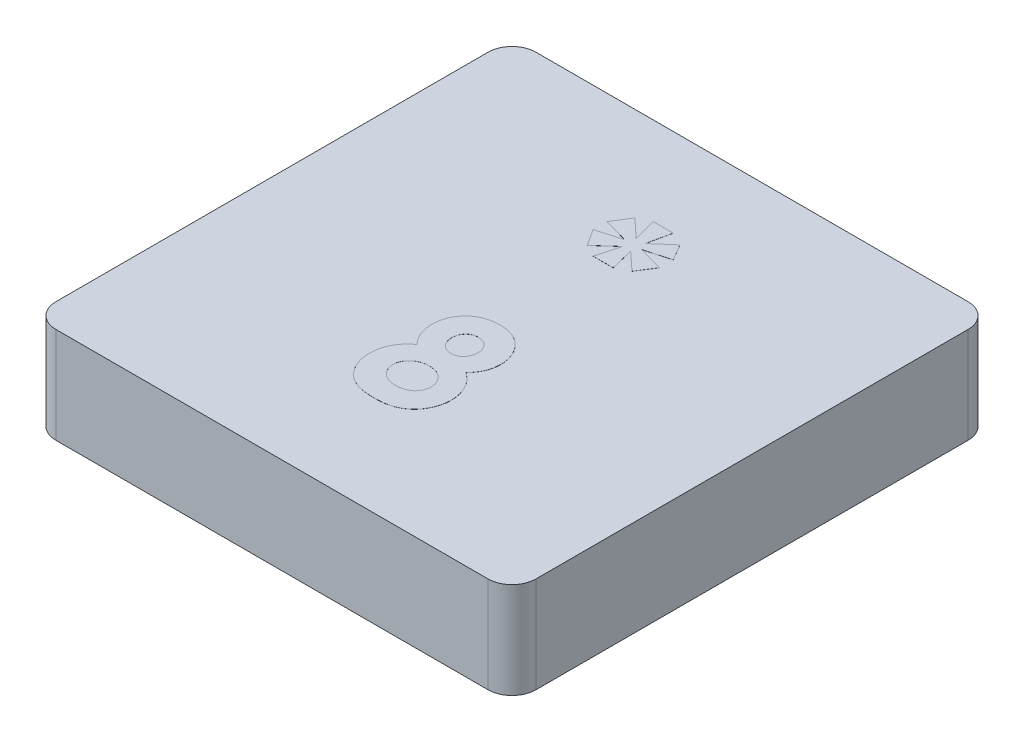
SolidWorks part; units mm, degrees
ref_plane "Front Plane" through (0, 0, 0) normal (0, 0, 1) x (1, 0, 0)
ref_plane "Top Plane" through (0, 0, 0) normal (0, 1, 0) x (1, 0, 0)
ref_plane "Right Plane" through (0, 0, 0) normal (1, 0, 0) x (0, 0, -1)
sketch "Sketch1" plane through (0, 0, 0) normal (0, 1, 0) x (1, 0, 0)
  line L0 (0, 0) -> (12.7, 0)
  line L1 (12.7, 0) -> (12.7, 12.7)
  line L2 (12.7, 12.7) -> (0, 12.7)
  line L3 (0, 12.7) -> (0, 0)
  dimension "D1" = 12.7
  dimension "D2" = 12.7
extrude "Boss-Extrude1" add sketch "Sketch1" along normal blind 2.54
fillet "Fillet1" radius 0.635 4 edges at (0, 1.27, -12.7) (12.7, 1.27, -12.7) (12.7, 1.27, 0) (0, 1.27, 0)
shell "Shell1" thickness 0.635 removed face at (6.35, 0, -6.35)
sketch "Sketch2" plane through (0, 1.905, 0) normal (0, -1, 0) x (-1, 0, 0)
  line L0 (-0.635, 6.35) -> (-12.065, 6.35) construction
  line L1 (-0.635, 12.065) -> (-0.635, 0.635) construction
  line L2 (-12.065, 0.635) -> (-12.065, 12.065) construction
  line L3 (-6.35, 0.635) -> (-6.35, 12.065) construction
  line L4 (-0.635, 0.635) -> (-12.065, 0.635) construction
  line L5 (-12.065, 12.065) -> (-0.635, 12.065) construction
  circle A0 centre (-6.35, 6.35) radius 2.54
  dimension "D1" = 5.08
extrude "Boss-Extrude2" add sketch "Sketch2" along normal up to surface (1.905 mm away) up to face at (6.35, 0, -6.35)
sketch "Sketch4" plane through (0, 2.54, 0) normal (0, 1, 0) x (1, 0, 0)
  line L0 (0, 12.065) -> (0, 0.635) construction
  line L1 (12.065, 12.7) -> (0.635, 12.7) construction
  line L2 (0.635, 0) -> (12.065, 0) construction
  text T0 "<b>8</b>"
  text T1 "<b>*</b>"
  dimension "D1" = 5.334
  dimension "D2" = 5.207
  dimension "D3" = 5.588
  dimension "D4" = 2.7178
extrude "Boss-Extrude4" add sketch "Sketch4" along normal blind 0.0025
